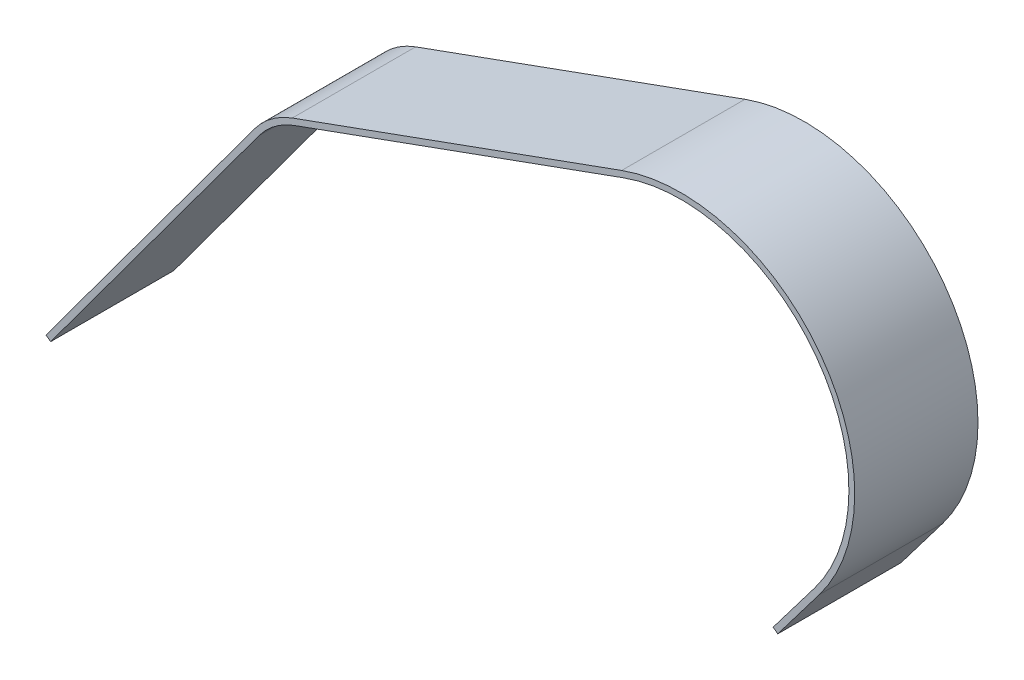
SolidWorks part; units mm, degrees
material "AISI 1020"
ref_plane "Front Plane" through (0, 0, 0) normal (0, 0, 1) x (1, 0, 0)
ref_plane "Top Plane" through (0, 0, 0) normal (0, 1, 0) x (1, 0, 0)
ref_plane "Right Plane" through (0, 0, 0) normal (1, 0, 0) x (0, 0, -1)
sketch "Sketch1" plane through (0, 0, 0) normal (0, 0, 1) x (1, 0, 0)
  line L0 (-36.5682, 0.9207) -> (143.9526, 66.3011)
  line L1 (-21.4316, -40.8727) -> (13.1807, -28.3369) construction
  line L6 (-36.5682, 0.9207) -> (-21.4316, -40.8727) construction
  line L14 (229.4691, -110.8747) -> (252.2647, -80.8348)
  line L15 (239.0655, -98.2286) -> (240.3301, -99.1882) construction
  line L19 (-57.2078, -14.4934) -> (-171.5307, -169.5402)
  line L23 (-163.3872, -155.8209) -> (-162.1095, -156.763) construction
  line L28 (143.9526, 66.3011) -> (194.1881, -72.4034) construction
  arc A0 (-57.2078, -14.4934) -> (-36.5682, 0.9207) centre (-21.4316, -40.8727) cw
  arc A10 (-190.1171, -186.0404) -> (-190.1067, -160.6404) centre (-190.1119, -173.3404) ccw construction
  arc A11 (143.9526, 66.3011) -> (252.2647, -80.8348) centre (176.3881, -23.2561) cw
  circle A12 centre (-21.4316, -40.8727) radius 6 construction
  circle A13 centre (231.071, -129.7727) radius 12.7 construction
  dimension "D5" = 44.45
  dimension "D3" = 15.875
  dimension "D2" = 95.25
  dimension "D1" = 15.875
extrude "Extrude-Thin1" add sketch "Sketch1" along normal blind 67.564 thin thin type one direction reverse wall 3.175
